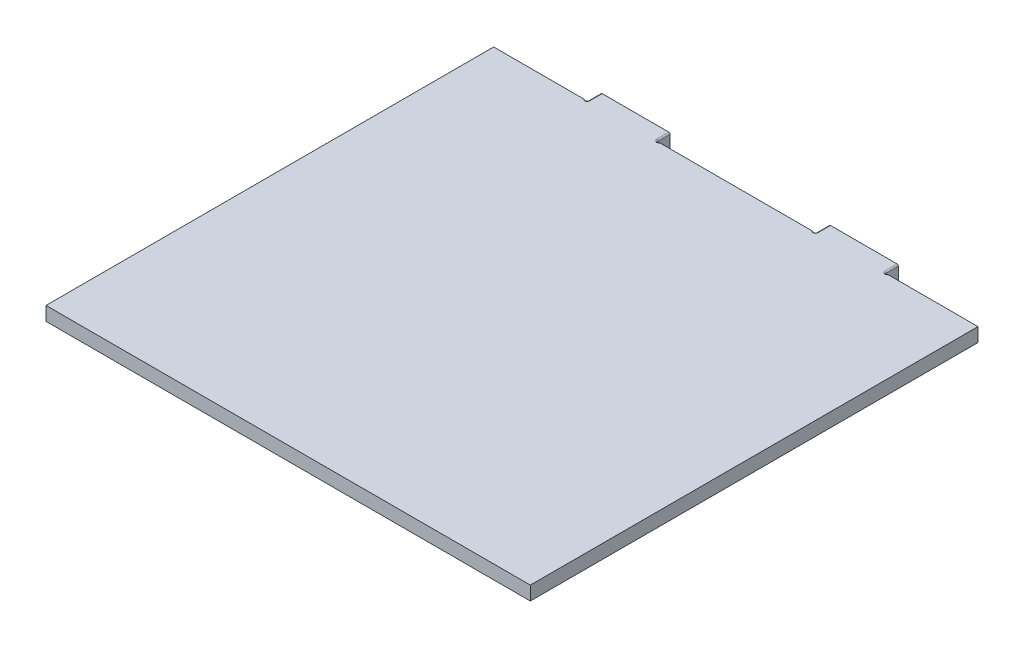
SolidWorks part; units mm, degrees
ref_plane "Front Plane" through (0, 0, 0) normal (0, 0, 1) x (1, 0, 0)
ref_plane "Top Plane" through (0, 0, 0) normal (0, 1, 0) x (1, 0, 0)
ref_plane "Right Plane" through (0, 0, 0) normal (1, 0, 0) x (0, 0, -1)
sketch "Sketch1" plane through (0, 0, 0) normal (0, 1, 0) x (1, 0, 0)
  line L1 (0, 0) -> (70, 0)
  line L2 (0, 0) -> (0, 64.7)
  line L3 (0, 64.7) -> (70, 64.7)
  line L4 (70, 0) -> (70, 64.7)
  dimension "D1" = 64.7
  dimension "D2" = 70
extrude "Boss-Extrude1" add sketch "Sketch1" along normal blind 2
sketch "Sketch2" plane through (0, 0, -64.7) normal (0, 0, -1) x (-1, 0, 0)
  line L0 (-70, 2) -> (0, 2) construction
  line L1 (-56.5, 2) -> (-46.5, 2)
  line L2 (-56.5, 2) -> (-56.5, -8)
  line L3 (-56.5, -8) -> (-46.5, -8)
  line L4 (-46.5, 2) -> (-46.5, -8)
  line L5 (-51.5, 2) -> (-51.5, -8) construction
  line L6 (-35, 2) -> (-35, -12.4484) construction
  line L7 (-54, -5) -> (-49, -5)
  line L8 (-54, -5) -> (-54, -1)
  line L9 (-54, -1) -> (-49, -1)
  line L10 (-49, -5) -> (-49, -1)
  line L11 (-54, -5) -> (-49, -1) construction
  line L12 (-54, -1) -> (-49, -5) construction
  line L13 (-16, -1) -> (-21, -5) construction
  line L14 (-16, -5) -> (-21, -1) construction
  line L15 (-18.5, 2) -> (-18.5, -8) construction
  line L16 (-21, -5) -> (-21, -1)
  line L17 (-16, -1) -> (-21, -1)
  line L18 (-16, -5) -> (-16, -1)
  line L19 (-16, -5) -> (-21, -5)
  line L20 (-23.5, 2) -> (-23.5, -8)
  line L21 (-13.5, -8) -> (-23.5, -8)
  line L22 (-13.5, 2) -> (-13.5, -8)
  line L23 (-13.5, 2) -> (-23.5, 2)
  line L24 (0, 2) -> (0, 0) construction
  line L25 (-70, 2) -> (-70, 0) construction
  point P8 (-51.5, -3)
  point P25 (-18.5, -3)
  dimension "D1" = 38
  dimension "D2" = 4
  dimension "D3" = 5
  dimension "D4" = 10
  dimension "D5" = 10
extrude "Boss-Extrude2" add sketch "Sketch2" along normal blind 2
fillet "Fillet2" radius 0.2 20 edges at (13.5, 1, -64.7) (56.5, 1, -64.7) (46.5, 1, -64.7) (23.5, 1, -64.7) (21, -1, -65.7) (21, -5, -65.7) (16, -5, -65.7) (13.5, 2, -65.7) (13.5, -8, -65.7) (23.5, -8, -65.7) (23.5, 2, -65.7) (16, -1, -65.7) (54, -1, -65.7) (54, -5, -65.7) (49, -5, -65.7) (56.5, 2, -65.7) (46.5, 2, -65.7) (46.5, -8, -65.7) (56.5, -8, -65.7) (49, -1, -65.7) tangent propagation no
